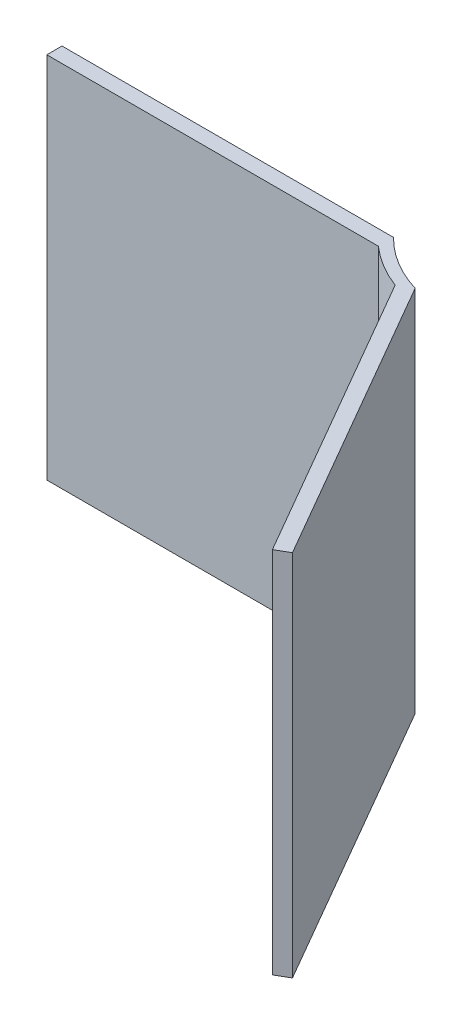
SolidWorks part; units mm, degrees
ref_plane "Plan de face" through (0, 0, 0) normal (0, 0, 1) x (1, 0, 0)
ref_plane "Plan de dessus" through (0, 0, 0) normal (0, 1, 0) x (1, 0, 0)
ref_plane "Plan de droite" through (0, 0, 0) normal (1, 0, 0) x (0, 0, -1)
sketch "Esquisse3" plane through (0, 0, 0) normal (0, 1, 0) x (1, 0, 0)
  line L0 (-150.1573, 0) -> (189.6273, 0) construction
  line L1 (-83.8395, -145.9242) -> (87.7229, 151.2306) construction
  line L2 (-78.0725, 135.2255) -> (117.7517, -203.9519) construction
  line L3 (-125, 131.2995) -> (-125, -153.5705) construction
  line L4 (-25, -24.4949) -> (-115, -24.4949)
  line L6 (-21.2883, 25.5051) -> (-23.9685, 25.5051)
  line L7 (-115, -24.4949) -> (-115, 25.5051)
  line L8 (-25, -24.4949) -> (-115, 25.5051) construction
  line L9 (-21.2883, 25.5051) -> (-115, -24.4949) construction
  line L10 (-23.9685, 25.5051) -> (-115, 25.5051)
  line L11 (34.0723, 8.0048) -> (79.5881, 86.8404)
  line L12 (36.2868, 111.8404) -> (79.5881, 86.8404)
  line L13 (-8.7132, 33.8981) -> (36.2868, 111.8404)
  line L14 (-10.1038, -33.5099) -> (35.4119, -112.3455)
  line L15 (78.7132, -87.3455) -> (35.4119, -112.3455)
  line L16 (33.7132, -9.4032) -> (78.7132, -87.3455)
  line L17 (-23.9685, 25.5051) -> (-25, -24.4949)
  line L18 (-8.7132, 33.8981) -> (34.0723, 8.0048)
  line L19 (-10.1038, -33.5099) -> (33.7132, -9.4032)
  line L20 (-25, -28.6182) -> (-115, -28.6182)
  line L21 (-115, -28.6182) -> (-115, -24.4949)
  line L22 (-13.5526, -35.5011) -> (31.9631, -114.3367)
  line L23 (31.9631, -114.3367) -> (35.4119, -112.3455)
  circle A0 centre (0, 0) radius 125
  circle A1 centre (0, 0) radius 35
  circle A2 centre (0, 0) radius 125
  circle A3 centre (0, 0) radius 125
  circle A4 centre (0, 0) radius 38
  point P9 (-69.0908, 0)
  point P32 (0, 0)
  point P33 (-115, -31.1065)
  point P35 (-23.9685, -29.3681)
  point P37 (0, 0)
  dimension "D1" = 250
  dimension "D4" = 70
  dimension "D2" = 120
  dimension "D3" = 120
  dimension "D5" = 10
  dimension "D6" = 50
  dimension "D7" = 90
  dimension "D9" = 3
  dimension "D8" = 3
extrude "Boss.-Extru.1" add sketch "Esquisse3" along normal blind 100 contours A4 L4 L21 L20 | L4 A4 L14 A1 | A4 L22 L23 L14 region at (-18.6168, 0, 30.8794) region at (-71.0566, 0, 26.5723) region at (11.4638, 0, 74.8797)
